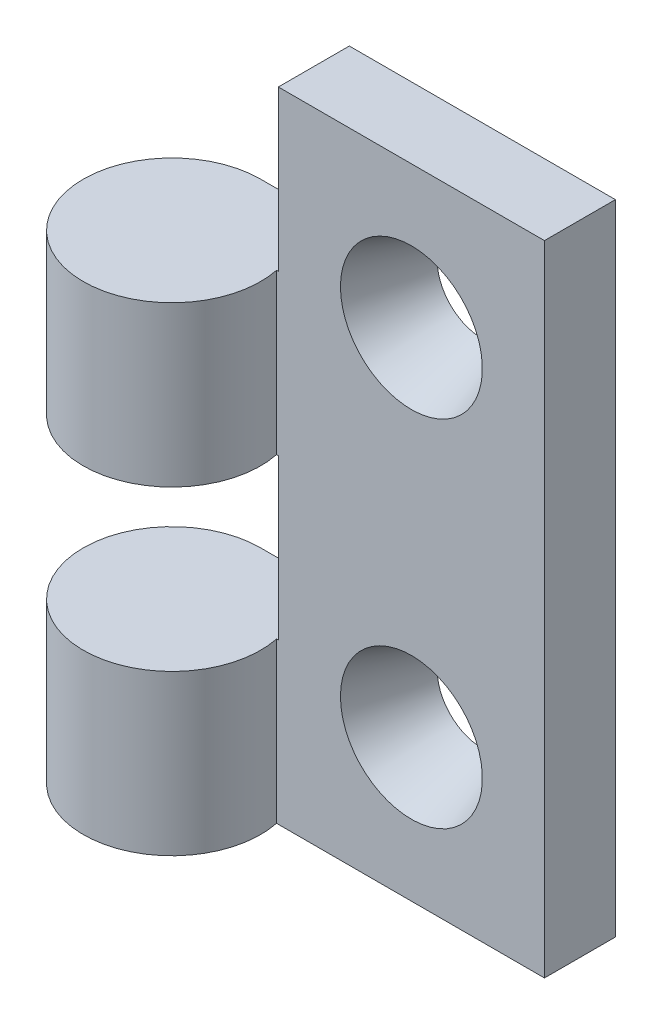
SolidWorks part; units mm, degrees
ref_plane "Front Plane" through (0, 0, 0) normal (1, 0, 0) x (0, 1, 0)
ref_plane "Top Plane" through (0, 0, 0) normal (0, 0, 1) x (0, 1, 0)
ref_plane "Right Plane" through (0, 0, 0) normal (0, 1, 0) x (-1, 0, 0)
sketch "Sketch3" plane through (0, 0, 0) normal (0, 0, 1) x (0, 1, 0)
  line L1 (0, 0) -> (36, 0)
  line L2 (0, 0) -> (0, 20)
  line L3 (0, 20) -> (36, 20)
  line L4 (36, 0) -> (36, 20)
  circle A0 centre (8, 7.5) radius 2.5
  circle A1 centre (28, 7.5) radius 2.5
  point P9 (8, 5)
  point P10 (28, 5)
  point P11 (5.5, 7.5)
  point P12 (30.5, 7.5)
  dimension "D3" = 5
  dimension "D7" = 5
  dimension "D8" = 5
  dimension "D1" = 36
  dimension "D2" = 20
  dimension "D4" = 5
  dimension "D5" = 5.5
  dimension "D6" = 5.5
extrude "Boss-Extrude2" add sketch "Sketch3" along normal blind 4
sketch "Sketch4" plane through (0, 0, 0) normal (0, -1, 0) x (1, 0, 0)
  line L0 (-20, 4) -> (-20, 0) construction
  circle A0 centre (-20, 5) radius 5
  dimension "D1" = 10
extrude "Boss-Extrude3" add sketch "Sketch4" against normal through all
sketch "Sketch5" plane through (0, 0, 0) normal (0, 0, -1) x (1, 0, 0)
  line L1 (-25, 0) -> (-25, -36) construction
  line L2 (-25, -9) -> (-15, -9)
  line L3 (-25, -9) -> (-25, -18)
  line L4 (-25, -18) -> (-15, -18)
  line L5 (-15, -9) -> (-15, -18)
  line L6 (0, 0) -> (0, -36) construction
  line L7 (-25, -36) -> (-15, -36)
  line L8 (-25, -36) -> (-25, -27)
  line L9 (-25, -27) -> (-15, -27)
  line L10 (-15, -36) -> (-15, -27)
  line L11 (-15, 0) -> (-25, 0) construction
  dimension "D1" = 15
  dimension "D2" = 15
  dimension "D3" = 9
  dimension "D4" = 9
  dimension "D5" = 9
chamfer "Chamfer1" distance 1.5 angle 70 2 edges at (-5, 28, 4) (-5, 8, 4) first distance on face at (-7.5505, 18, 4)
extrude "Cut-Extrude2" cut sketch "Sketch5" against normal through all contours L3 L4 L5 L2 | L8 L9 L10 L7
